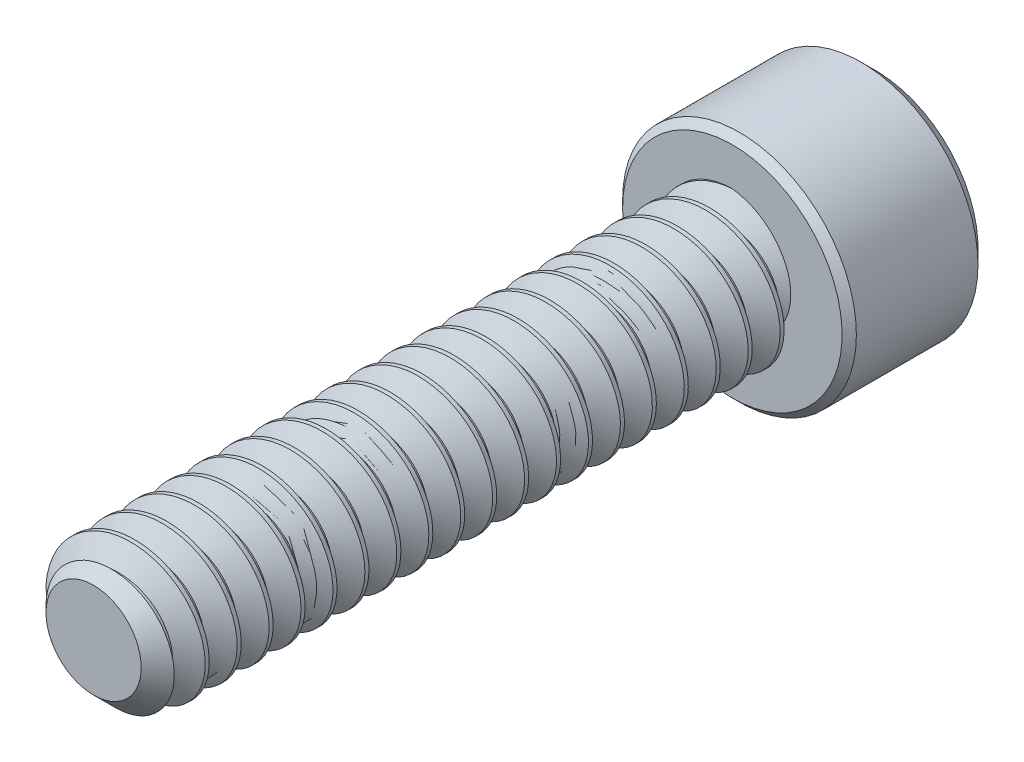
SolidWorks part; units mm, degrees
ref_plane "Front Plane" through (0, 0, 0) normal (0, 0, 1) x (1, 0, 0)
ref_plane "Top Plane" through (0, 0, 0) normal (0, 1, 0) x (1, 0, 0)
ref_plane "Right Plane" through (0, 0, 0) normal (1, 0, 0) x (0, 0, -1)
sketch "Sketch1" plane through (0, 0, 0) normal (0, 0, 1) x (1, 0, 0)
  line L0 (0, 1.4224) -> (0, -1.4224) construction
  circle A0 centre (0, 0) radius 1.4224
  dimension "OD" = 2.8448
extrude "Extrude1" add sketch "Sketch1" against normal blind 12.7
sketch "Sketch2" plane through (0, 0, 0) normal (0, 0, 1) x (1, 0, 0)
  circle A0 centre (0, 0) radius 1.4224 construction
  circle A1 centre (0, 0) radius 1.4224
curve "Helix/Spiral1" pitch 0.635 height 13.335 radius 1.4224 centre (0, 0, 0) axis (0, 0, -1) start towards (0, 1, 0) parameters "pitch"=0.635
chamfer "Chamfer3" distance 0.4763 angle 45 1 edges at (1.4224, 0, 0)
sketch "Sketch3" plane through (0, 0, 0) normal (1, 0, 0) x (0, 0, -1)
  line L0 (-0.5556, 1.4224) -> (-0.3175, 1.01)
  line L1 (-0.3175, 1.01) -> (-0.2381, 1.01)
  line L2 (-0.2381, 1.01) -> (0, 1.4224)
  line L3 (-0.5556, 1.4224) -> (0, 1.4224)
  line L4 (-0.2778, 1.4224) -> (-0.2778, 1.01) construction
  line L5 (-0.4366, 1.2162) -> (-0.1191, 1.2162) construction
  line L6 (0, 1.4224) -> (0, -1.4224) construction
  dimension "D1" = 0.0794
  dimension "D2" = 0.3175
  dimension "D3" = 60
sweep "Cut-Sweep1" cut profiles "Sketch3" path "Helix/Spiral1"
sketch "Sketch6" plane through (0, 0, -12.7) normal (0, 0, -1) x (-1, 0, 0)
  circle A0 centre (0, 0) radius 2.3241
  dimension "head dia" = 4.6482
extrude "Extrude2" add sketch "Sketch6" along normal blind 2.8448
sketch "Sketch7" plane through (0, 0, -15.5448) normal (0, 0, -1) x (-1, 0, 0)
  line L1 (0, 1.3748) -> (-1.1906, 0.6874)
  line L2 (-1.1906, 0.6874) -> (-1.1906, -0.6874)
  line L3 (-1.1906, -0.6874) -> (0, -1.3748)
  line L4 (0, -1.3748) -> (1.1906, -0.6874)
  line L5 (1.1906, -0.6874) -> (1.1906, 0.6874)
  line L6 (1.1906, 0.6874) -> (0, 1.3748)
  circle A0 centre (0, 0) radius 1.1906 construction
  dimension "hex dia" = 2.3813
extrude "Cut-Extrude1" cut sketch "Sketch7" against normal blind 1.7859
sketch "Sketch8" plane through (0, 0, -15.5448) normal (0, 0, -1) x (-1, 0, 0)
  circle A0 centre (0, 0) radius 1.3748
extrude "Cut-Extrude2" cut sketch "Sketch8" against normal blind 0.2845 draft 45
chamfer "Chamfer1" distance 0.2845 angle 45 1 edges at (-2.3241, 0, -15.5448)
chamfer "Chamfer2" distance 0.1422 angle 45 1 edges at (-2.3241, 0, -12.7)
equation "\"D3@Helix/Spiral1\" = \"screw length@Extrude1\"+\"pitch@Helix/Spiral1\""
equation "\"D1@Sketch3\" = \"pitch@Helix/Spiral1\"*.125"
equation "\"D2@Sketch3\" = \"pitch@Helix/Spiral1\"*.5"
equation "\"D1@Cut-Extrude1\" = \"hex dia@Sketch7\"*.75"
equation "\"D1@Chamfer1\" = \"head depth@Extrude2\"/10"
equation "\"D1@Sketch9\" = \"pitch@Helix/Spiral1\"*5.5"
equation "\"D1@Chamfer2\" = \"D1@Chamfer1\"/2"
equation "\"D1@Cut-Extrude2\" = \"D1@Chamfer2\"*2"
equation "\"D1@Chamfer3\" = \"pitch@Helix/Spiral1\"*.750"
equation "\"D2@Sketch9\" = \"head depth@Extrude2\""
equation "\"D3@Sketch9\" = \"head dia@Sketch6\""
equation "\"D4@Sketch9\" = \"screw length@Extrude1\""
